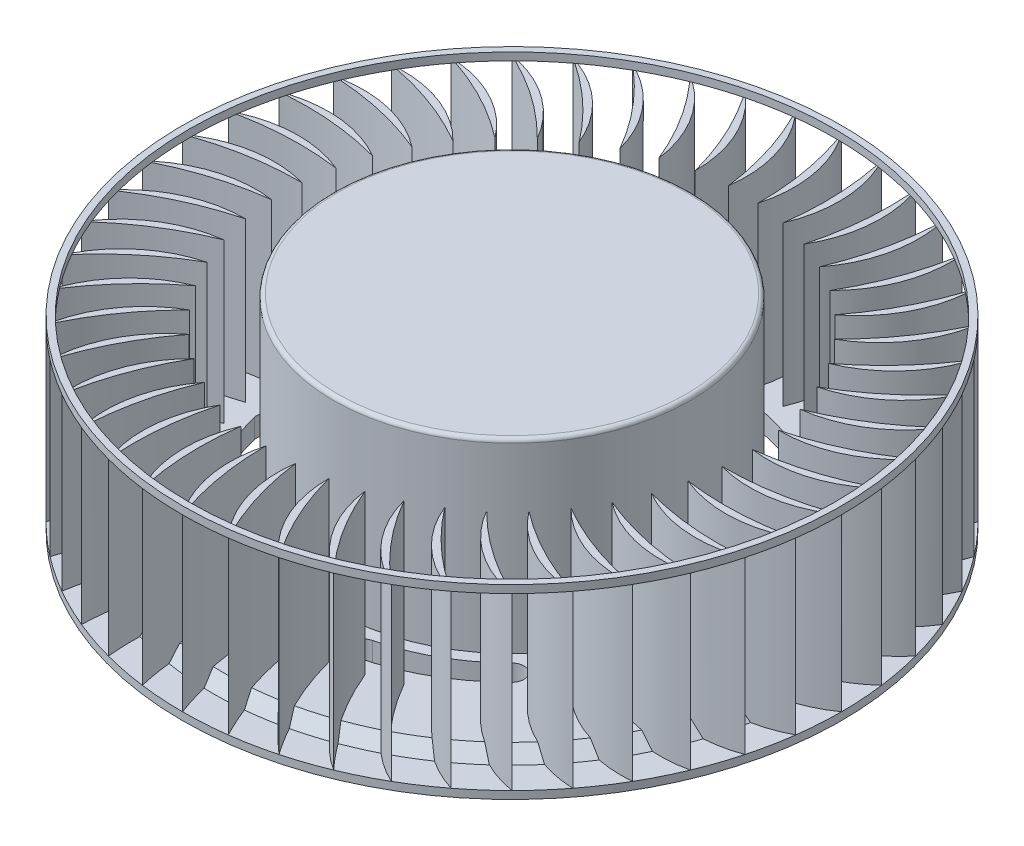
SolidWorks part; units mm, degrees
material "PET"
ref_plane "Спереди" through (0, 0, 0) normal (0, 0, 1) x (1, 0, 0)
ref_plane "Сверху" through (0, 0, 0) normal (0, 1, 0) x (1, 0, 0)
ref_plane "Справа" through (0, 0, 0) normal (1, 0, 0) x (0, 0, -1)
sketch "Эскиз1" plane through (0, 0, 0) normal (0, 1, 0) x (1, 0, 0)
  circle A0 centre (0, 0) radius 42.5
  dimension "D1" = 85
extrude "Бобышка-Вытянуть1" add sketch "Эскиз1" along normal blind 1
sketch "Эскиз2" plane through (0, 1, 0) normal (0, 1, 0) x (1, 0, 0)
  circle A0 centre (0, 0) radius 38.5
  circle A1 centre (0, 0) radius 42.5 construction
  dimension "D1" = 4
extrude "Бобышка-Вытянуть2" add sketch "Эскиз2" along normal blind 1.5
chamfer "Фаска1" distance 1.5 angle 45 1 edges at (0, 2.5, 38.5)
sketch "Эскиз3" plane through (0, 2.5, 0) normal (0, 1, 0) x (1, 0, 0)
  circle A0 centre (0, 0) radius 23
  dimension "D1" = 46
extrude "Бобышка-Вытянуть3" add sketch "Эскиз3" along normal offset from surface (24 mm away) 26.5 up to face at (0, 0, 42.5)
fillet "Скругление1" radius 0.5 1 edges at (0, 26.5, 23)
sketch "Эскиз4" plane through (0, 0, 0) normal (0, 1, 0) x (1, 0, 0)
  line L0 (0, 0) -> (0, 32.8652) construction
  line L1 (1.745, 36.059) -> (-34.8011, 29.6149) construction
  line L2 (0, 42.5) -> (2.3082, 29.4096) construction
  circle A0 centre (0, 0) radius 29.5 construction
  circle A1 centre (0, 0) radius 42.5 construction
  arc A2 (0, 42.5) -> (2.3082, 29.4096) centre (-34.8011, 29.6149) cw
  arc A3 (2.3082, 29.4096) -> (0, 42.5) centre (-12.6076, 33.5282) ccw
  point P9 (2.6313, 36.2153)
  dimension "D1" = 59
  dimension "D2" = 85
  dimension "D3" = 10
  dimension "D4" = 0.9
  dimension "D5" = 0.6
extrude "Бобышка-Вытянуть4" add sketch "Эскиз4" along normal blind 23
pattern_circular "Круговой массив1" count 48 over 360 about axis through (0, 1, 0) along (0, 1, 0) of "Бобышка-Вытянуть4"
sketch "Эскиз5" plane through (0, 0, 0) normal (0, -1, 0) x (1, 0, 0)
  circle A0 centre (0, 0) radius 20
  dimension "D1" = 40
extrude "Вырез-Вытянуть1" cut sketch "Эскиз5" against normal blind 1.2
chamfer "Фаска2" distance 1.2 angle 45 1 edges at (0, 0, -20)
sketch "Эскиз6" plane through (0, 1.2, 0) normal (0, -1, 0) x (1, 0, 0)
  circle A0 centre (0, 0) radius 20
  dimension "D1" = 40
extrude "Вырез-Вытянуть2" cut sketch "Эскиз6" against normal blind 8.5
sketch "Esboço1" plane through (0, 2.5, 0) normal (0, 1, 0) x (1, 0, 0)
  circle A0 centre (0, 0) radius 26 construction
  arc A1 (0, 26) -> (13.5393, 22.1966) centre (0, 0) cw construction
  arc A6 (14.3342, 23.4997) -> (0, 27.5265) centre (0, 0) ccw
  arc A7 (12.7444, 20.8934) -> (0, 24.4735) centre (0, 0) ccw
  arc A8 (12.7444, 20.8934) -> (14.3342, 23.4997) centre (13.5393, 22.1966) ccw
  arc A9 (0, 27.5265) -> (0, 24.4735) centre (0, 26) ccw
  arc A10 (18.3848, 18.3848) -> (25.2691, 6.1216) centre (0, 0) cw construction
  arc A11 (26.7526, 6.481) -> (19.4642, 19.4642) centre (0, 0) ccw
  arc A12 (23.7855, 5.7622) -> (17.3054, 17.3054) centre (0, 0) ccw
  arc A13 (23.7855, 5.7622) -> (26.7526, 6.481) centre (25.2691, 6.1216) ccw
  arc A14 (19.4642, 19.4642) -> (17.3054, 17.3054) centre (18.3848, 18.3848) ccw
  arc A15 (26, 0) -> (22.1966, -13.5393) centre (0, 0) cw construction
  arc A16 (23.4997, -14.3342) -> (27.5265, 0) centre (0, 0) ccw
  arc A17 (20.8934, -12.7444) -> (24.4735, 0) centre (0, 0) ccw
  arc A18 (20.8934, -12.7444) -> (23.4997, -14.3342) centre (22.1966, -13.5393) ccw
  arc A19 (27.5265, 0) -> (24.4735, 0) centre (26, 0) ccw
  arc A20 (18.3848, -18.3848) -> (6.1216, -25.2691) centre (0, 0) cw construction
  arc A21 (6.481, -26.7526) -> (19.4642, -19.4642) centre (0, 0) ccw
  arc A22 (5.7622, -23.7855) -> (17.3054, -17.3054) centre (0, 0) ccw
  arc A23 (5.7622, -23.7855) -> (6.481, -26.7526) centre (6.1216, -25.2691) ccw
  arc A24 (19.4642, -19.4642) -> (17.3054, -17.3054) centre (18.3848, -18.3848) ccw
  arc A25 (0, -26) -> (-13.5393, -22.1966) centre (0, 0) cw construction
  arc A26 (-14.3342, -23.4997) -> (0, -27.5265) centre (0, 0) ccw
  arc A27 (-12.7444, -20.8934) -> (0, -24.4735) centre (0, 0) ccw
  arc A28 (-12.7444, -20.8934) -> (-14.3342, -23.4997) centre (-13.5393, -22.1966) ccw
  arc A29 (0, -27.5265) -> (0, -24.4735) centre (0, -26) ccw
  arc A30 (-18.3848, -18.3848) -> (-25.2691, -6.1216) centre (0, 0) cw construction
  arc A31 (-26.7526, -6.481) -> (-19.4642, -19.4642) centre (0, 0) ccw
  arc A32 (-23.7855, -5.7622) -> (-17.3054, -17.3054) centre (0, 0) ccw
  arc A33 (-23.7855, -5.7622) -> (-26.7526, -6.481) centre (-25.2691, -6.1216) ccw
  arc A34 (-19.4642, -19.4642) -> (-17.3054, -17.3054) centre (-18.3848, -18.3848) ccw
  arc A35 (-26, 0) -> (-22.1966, 13.5393) centre (0, 0) cw construction
  arc A36 (-23.4997, 14.3342) -> (-27.5265, 0) centre (0, 0) ccw
  arc A37 (-20.8934, 12.7444) -> (-24.4735, 0) centre (0, 0) ccw
  arc A38 (-20.8934, 12.7444) -> (-23.4997, 14.3342) centre (-22.1966, 13.5393) ccw
  arc A39 (-27.5265, 0) -> (-24.4735, 0) centre (-26, 0) ccw
  arc A40 (-18.3848, 18.3848) -> (-6.1216, 25.2691) centre (0, 0) cw construction
  arc A41 (-6.481, 26.7526) -> (-19.4642, 19.4642) centre (0, 0) ccw
  arc A42 (-5.7622, 23.7855) -> (-17.3054, 17.3054) centre (0, 0) ccw
  arc A43 (-5.7622, 23.7855) -> (-6.481, 26.7526) centre (-6.1216, 25.2691) ccw
  arc A44 (-19.4642, 19.4642) -> (-17.3054, 17.3054) centre (-18.3848, 18.3848) ccw
  point P6 (7.0317, 25.0311)
  point P16 (22.6718, 12.7275)
  point P23 (25.0311, -7.0317)
  point P30 (12.7275, -22.6718)
  point P37 (-7.0317, -25.0311)
  point P44 (-22.6718, -12.7275)
  point P51 (-25.0311, 7.0317)
  point P58 (-12.7275, 22.6718)
  point P63 (0, 0)
  dimension "D1" = 52
  dimension "D2" = 8
extrude "Corte-extrusão1" cut sketch "Esboço1" against normal blind 10
sketch "Esboço3" plane through (0, 23, 0) normal (0, 1, 0) x (1, 0, 0)
  circle A0 centre (0, 0) radius 42.5
  circle A1 centre (0, 0) radius 41.6578
extrude "Ressalto-extrusão6" add sketch "Esboço3" along normal blind 1
